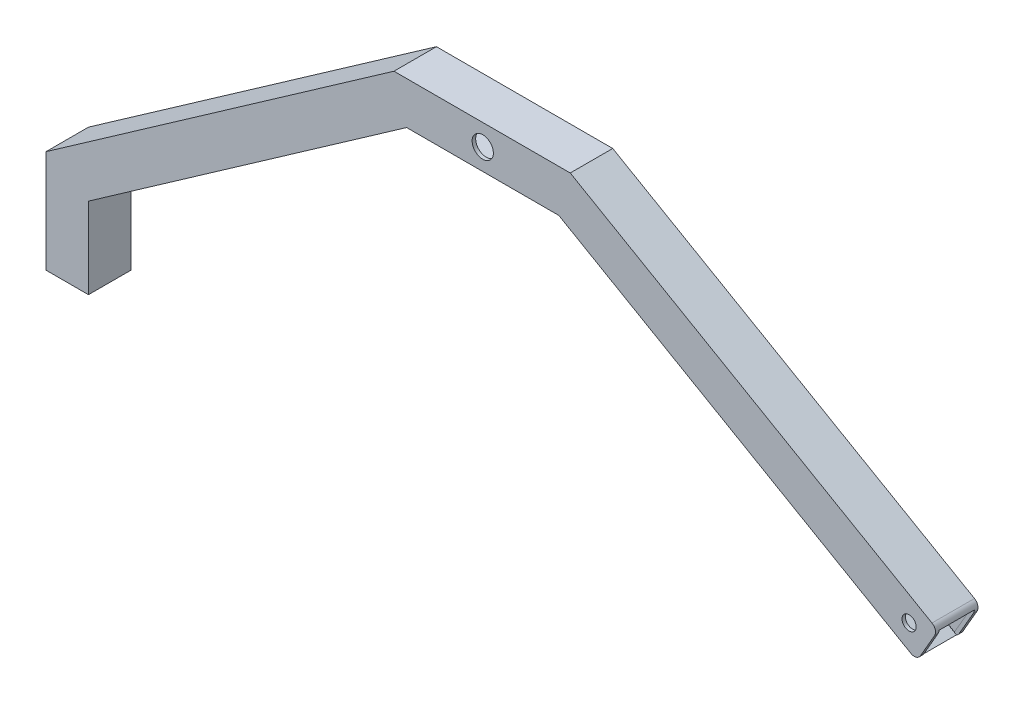
SolidWorks part; units mm, degrees
material "1060 Alloy"
ref_plane "Front Plane" through (0, 0, 0) normal (0, 0, 1) x (1, 0, 0)
ref_plane "Top Plane" through (0, 0, 0) normal (0, 1, 0) x (1, 0, 0)
ref_plane "Right Plane" through (0, 0, 0) normal (1, 0, 0) x (0, 0, -1)
sketch "Sketch2" plane through (0, 0, 0) normal (0, 0, 1) x (1, 0, 0)
  line L2 (-28.0029, 3.2102) -> (-126.3012, -65.6189)
  line L3 (-28.0029, 3.2102) -> (21.7951, 3.2102)
  line L5 (-24.4214, -8.7883) -> (18.5771, -8.7883)
  line L7 (-126.3012, -94.6189) -> (-114.3012, -94.6189) construction
  line L10 (-114.3012, -71.7228) -> (-24.4214, -8.7883)
  line L13 (-126.3012, -65.6189) -> (-126.3012, -94.6189)
  line L14 (-126.3012, -94.6189) -> (-114.3012, -94.6189)
  line L15 (-114.3012, -71.7228) -> (-114.3012, -94.6189)
  line L16 (21.7951, 3.2102) -> (125.7181, -56.7898)
  line L17 (125.7181, -56.7898) -> (119.7181, -67.1821)
  line L18 (119.7181, -67.1821) -> (18.5771, -8.7883)
  line L38 (-126.3012, -94.6189) -> (-114.3012, -94.6189)
  point P2 (0, 1.2778)
  point P6 (0, 1.2778)
  dimension "D2" = 29
  dimension "D3" = 12
  dimension "D4" = 120
  dimension "D5" = 145
  dimension "D7" = 120
  dimension "D8" = 150
  dimension "D9" = 90
  dimension "D10" = 12
extrude "Boss-Extrude1" add sketch "Sketch2" along normal blind 12 contours L18 L17 L16 L3 L2 L13 L14 L15 L10 L5 region at (-3.1039, 0.5068, 0)
shell "Shell1" thickness 1 removed face at (-120.3012, -94.6189, 6)
sketch "Sketch3" plane through (0, 0, 12) normal (0, 0, 1) x (1, 0, 0)
  line L0 (-24.4214, -8.7883) -> (18.5771, -8.7883) construction
  line L1 (119.7181, -67.1821) -> (18.5771, -8.7883) construction
  line L2 (125.7181, -56.7898) -> (119.7181, -67.1821) construction
  circle A0 centre (-2.9222, -2.7883) radius 3
  circle A1 centre (117.5219, -58.9859) radius 2
  dimension "D1" = 6
  dimension "D3" = 4
  dimension "D2" = 6
  dimension "D4" = 6
  dimension "D5" = 6
extrude "Cut-Extrude1" cut sketch "Sketch3" against normal blind 12
sketch "Sketch4" plane through (118.8793, -68.635, 0) normal (0.866, -0.5, 0) x (0, 0, -1)
  line L1 (-11.0371, 12.6336) -> (-1.0371, 12.6336)
  line L2 (-11.0371, 12.6336) -> (-11.0371, 2.6336)
  line L3 (-11.0371, 2.6336) -> (-1.0371, 2.6336)
  line L4 (-1.0371, 12.6336) -> (-1.0371, 2.6336)
  line L5 (-11.0371, 12.6336) -> (-1.0371, 2.6336) construction
  line L6 (-11.0371, 2.6336) -> (-1.0371, 12.6336) construction
  point P0 (-6.0371, 7.6336)
  dimension "D1" = 10
  dimension "D2" = 10
extrude "Cut-Extrude2" cut sketch "Sketch4" against normal blind 12
fillet "Fillet1" radius 2 2 edges at (119.7181, -67.1821, 6) (125.7181, -56.7898, 6)
